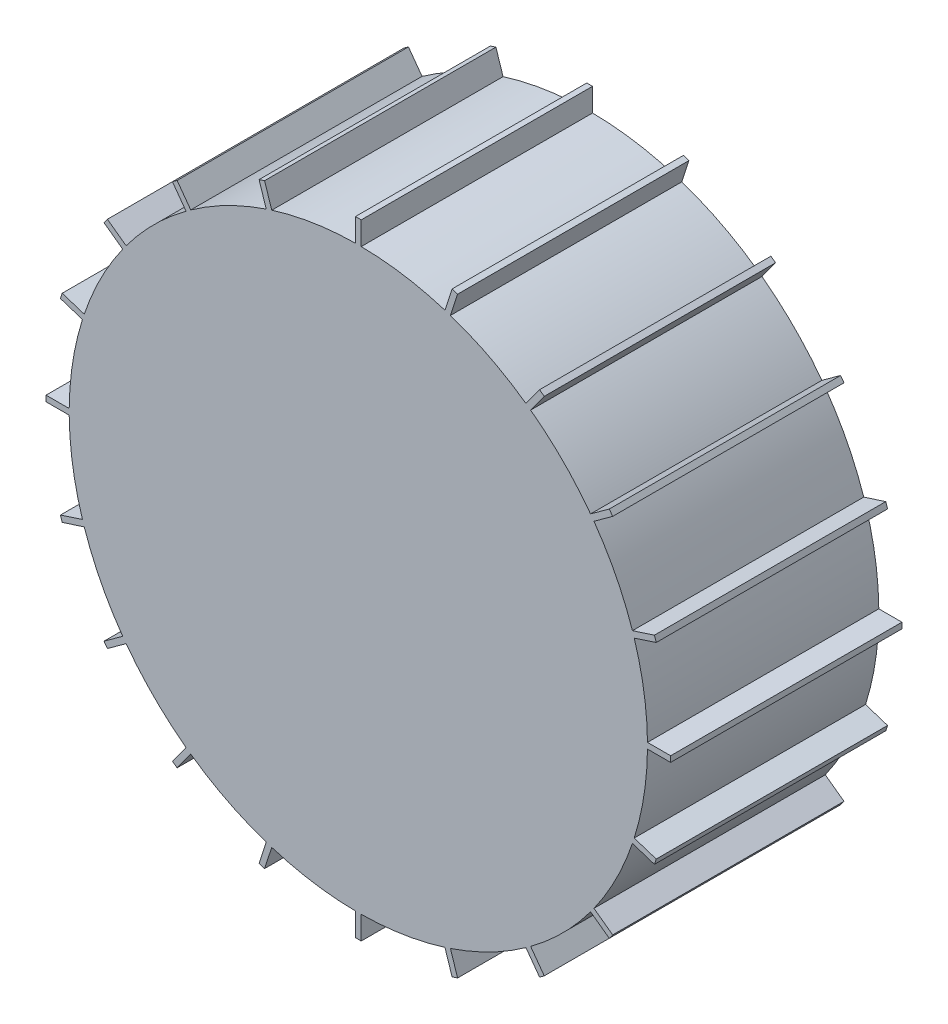
SolidWorks part; units mm, degrees
ref_plane "Front Plane" through (0, 0, 0) normal (0, 0, 1) x (1, 0, 0)
ref_plane "Top Plane" through (0, 0, 0) normal (0, 1, 0) x (1, 0, 0)
ref_plane "Right Plane" through (0, 0, 0) normal (1, 0, 0) x (0, 0, -1)
sketch "Sketch1" plane through (0, 0, 0) normal (0, 0, 1) x (1, 0, 0)
  circle A0 centre (0, 0) radius 250
  dimension "D1" = 500
extrude "Wheel Base" add sketch "Sketch1" along normal blind 200
ref_axis "Axis1" through (0, 0, 200) along (0, 0, -1)
sketch "Sketch3" plane through (0, 0, 0) normal (0, 1, 0) x (1, 0, 0)
  line L0 (0, 0) -> (0, -200) construction
  line L2 (2.5, -200) -> (-2.5, -200)
  line L3 (2.5, -200) -> (2.5, 0)
  line L4 (2.5, 0) -> (-2.5, 0)
  line L5 (-2.5, -200) -> (-2.5, 0)
  line L6 (2.5, -200) -> (-2.5, 0) construction
  line L7 (2.5, 0) -> (-2.5, -200) construction
  point P3 (0, -100)
  dimension "D1" = 200
  dimension "D2" = 200
  dimension "D3" = 5
extrude "Grouser" add sketch "Sketch3" along normal blind 270
pattern_circular "Grousers" count 20 over 360 about axis through (0, 0, 200) along (0, 0, -1) of "Grouser"
equation "\"Wheel_Diameter\"= 50cm"
equation "\"D1@Sketch1\"=\"Wheel_Diameter\""
equation "\"Wheel_Width\" = 20cm"
equation "\"D1@Wheel Base\"=\"Wheel_Width\""
equation "\"D1@Sketch3\"=\"Wheel_Width\""
equation "\"D2@Sketch3\"=\"Wheel_Width\""
equation "\"Grouser_width\"= 5mm"
equation "\"D3@Sketch3\"=\"Grouser_width\""
equation "\"Grouser_height\"= 2cm"
equation "\"D1@Grouser\" = \"Wheel_Diameter\" / 2 + \"Grouser_height\""
equation "\"Number_of_Grousers\"= 20"
equation "\"D1@Grousers\" = \"Number_of_Grousers\""
